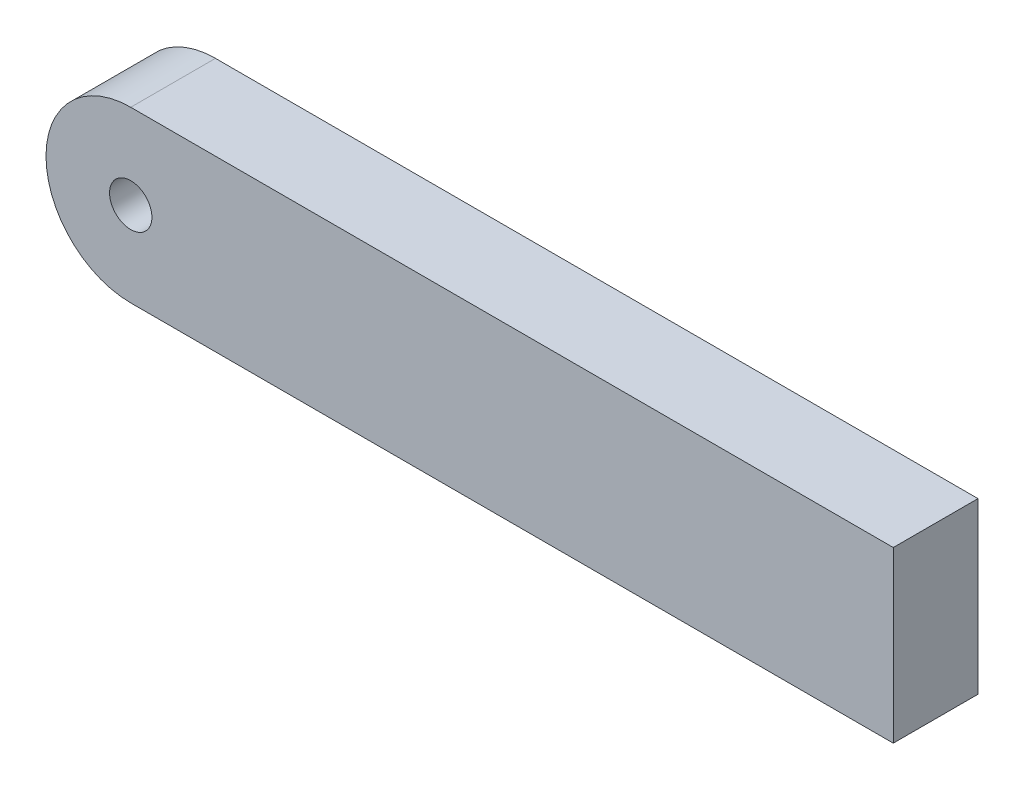
SolidWorks part; units mm, degrees
ref_plane "Front Plane" through (0, 0, 0) normal (0, 0, 1) x (1, 0, 0)
ref_plane "Top Plane" through (0, 0, 0) normal (0, 1, 0) x (1, 0, 0)
ref_plane "Right Plane" through (0, 0, 0) normal (1, 0, 0) x (0, 0, -1)
sketch "Sketch1" plane through (0, 0, 0) normal (0, 0, 1) x (1, 0, 0)
  line L0 (0, 10) -> (180, 10)
  line L1 (180, -10) -> (0, -10)
  line L2 (90, 10) -> (90, -10)
  circle A0 centre (0, 0) radius 2.5
  circle A1 centre (180, 0) radius 2.5
  arc A2 (0, -10) -> (0, 10) centre (0, 0) cw
  arc A3 (180, -10) -> (180, 10) centre (180, 0) ccw
  point P9 (-10, 0)
  dimension "D2" = 5
  dimension "D3" = 10
  dimension "D1" = 180
extrude "Boss-Extrude1" add sketch "Sketch1" along normal blind 10 contours A2 L1 L2 L0 A0 region at (41.4635, 0, 0)
